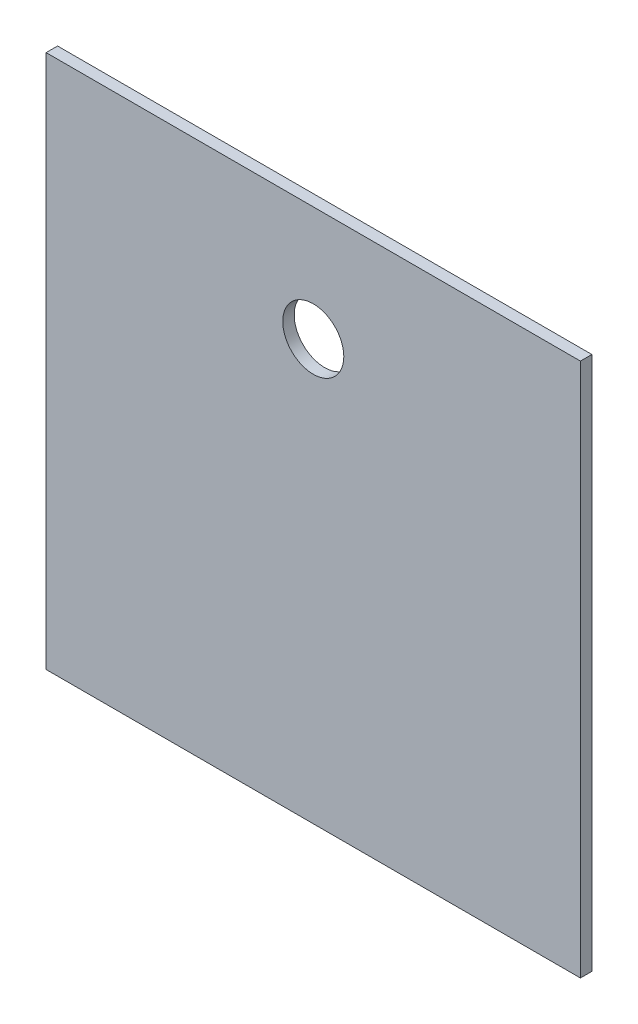
SolidWorks part; units mm, degrees
material "3.0205 (EN-AW 1200)"
ref_plane "Piano frontale" through (0, 0, 0) normal (0, 0, 1) x (1, 0, 0)
ref_plane "Piano superiore" through (0, 0, 0) normal (0, 1, 0) x (1, 0, 0)
ref_plane "Piano destro" through (0, 0, 0) normal (1, 0, 0) x (0, 0, -1)
sketch "Schizzo1" plane through (0, 0, 0) normal (0, 0, 1) x (1, 0, 0)
  line L1 (-350, 350) -> (350, 350)
  line L2 (-350, 350) -> (-350, -350)
  line L3 (-350, -350) -> (350, -350)
  line L4 (350, 350) -> (350, -350)
  line L5 (-350, 350) -> (350, -350) construction
  line L6 (-350, -350) -> (350, 350) construction
  point P0 (0, 0)
  dimension "D1" = 700
  dimension "D2" = 700
extrude "Estrusione-Estrusione1" add sketch "Schizzo1" along normal blind 15
sketch "Schizzo2" plane through (0, 0, 15) normal (0, 0, 1) x (1, 0, 0)
  circle A0 centre (0, 200) radius 40
  dimension "D2" = 80
  dimension "D1" = 200
extrude "Taglio-Estrusione1" cut sketch "Schizzo2" against normal blind 15
